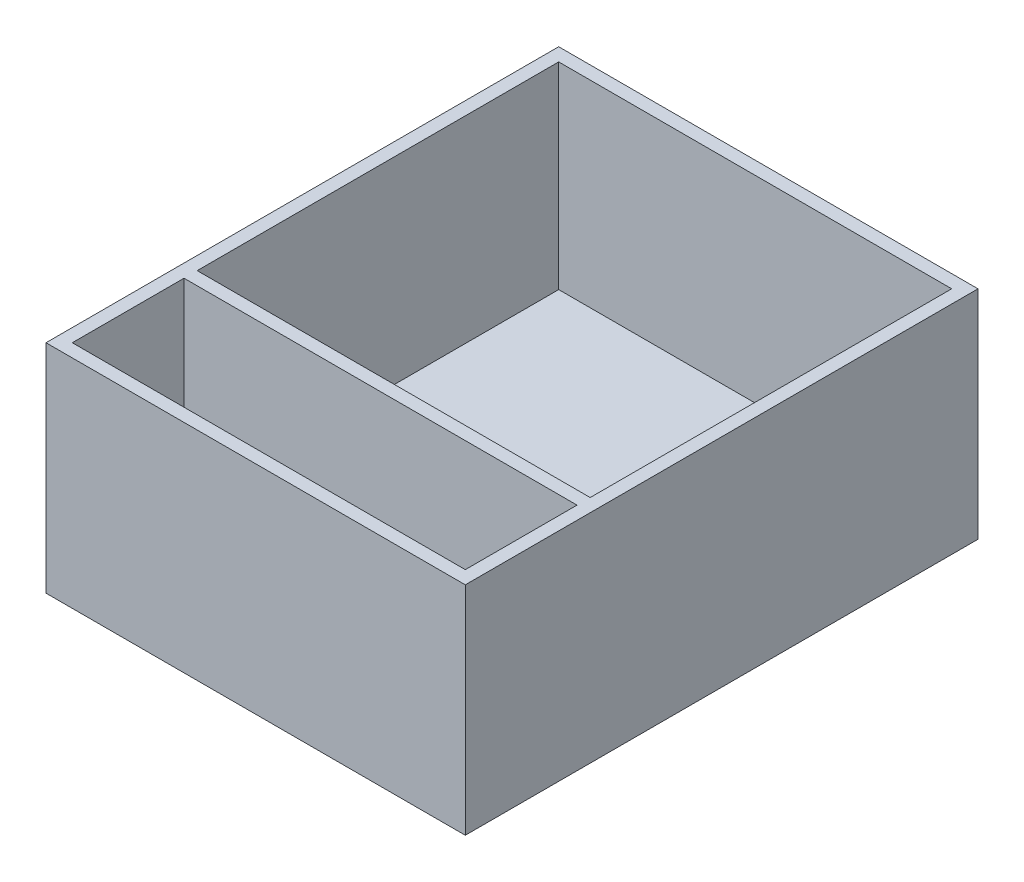
SolidWorks part; units mm, degrees
ref_plane "Front Plane" through (0, 0, 0) normal (0, 0, 1) x (1, 0, 0)
ref_plane "Top Plane" through (0, 0, 0) normal (0, 1, 0) x (1, 0, 0)
ref_plane "Right Plane" through (0, 0, 0) normal (1, 0, 0) x (0, 0, -1)
sketch "Sketch1" plane through (0, 0, 0) normal (0, 1, 0) x (1, 0, 0)
  line L0 (2.6203, -51.9542) -> (2.6263, -51.9542)
  line L1 (2.6263, -51.9542) -> (2.6323, -51.9562)
  line L2 (2.6323, -51.9562) -> (2.6393, -51.9572)
  line L3 (2.6393, -51.9572) -> (2.6443, -51.9602)
  line L4 (2.6443, -51.9602) -> (2.6513, -51.9622)
  line L5 (2.6513, -51.9622) -> (2.6563, -51.9672)
  line L6 (2.6563, -51.9672) -> (2.6613, -51.9702)
  line L7 (2.6613, -51.9702) -> (2.6653, -51.9752)
  line L8 (2.6653, -51.9752) -> (2.6703, -51.9792)
  line L9 (2.6703, -51.9792) -> (2.6743, -51.9852)
  line L10 (2.6743, -51.9852) -> (2.6783, -51.9902)
  line L11 (2.6783, -51.9902) -> (2.6803, -51.9962)
  line L12 (2.6803, -51.9962) -> (2.6843, -52.0022)
  line L13 (2.6843, -52.0022) -> (2.6853, -52.0082)
  line L14 (2.6853, -52.0082) -> (2.6873, -52.0142)
  line L15 (2.6873, -52.0142) -> (2.6873, -52.0212)
  line L16 (2.6873, -52.0212) -> (2.6883, -52.0272)
  line L17 (2.6883, -52.0272) -> (2.6883, -53.0272)
  line L18 (2.6883, -53.0272) -> (2.6873, -53.0342)
  line L19 (2.6873, -53.0342) -> (2.6873, -53.0402)
  line L20 (2.6873, -53.0402) -> (2.6853, -53.0472)
  line L21 (2.6853, -53.0472) -> (2.6843, -53.0532)
  line L22 (2.6843, -53.0532) -> (2.6803, -53.0592)
  line L23 (2.6803, -53.0592) -> (2.6783, -53.0652)
  line L24 (2.6783, -53.0652) -> (2.6743, -53.0702)
  line L25 (2.6743, -53.0702) -> (2.6703, -53.0762)
  line L26 (2.6703, -53.0762) -> (2.6653, -53.0802)
  line L27 (2.6653, -53.0802) -> (2.6613, -53.0852)
  line L28 (2.6613, -53.0852) -> (2.6563, -53.0882)
  line L29 (2.6563, -53.0882) -> (2.6513, -53.0922)
  line L30 (2.6513, -53.0922) -> (2.6443, -53.0952)
  line L31 (2.6443, -53.0952) -> (2.6393, -53.0982)
  line L32 (2.6393, -53.0982) -> (2.6323, -53.0992)
  line L33 (2.6323, -53.0992) -> (2.6263, -53.1012)
  line L34 (2.6263, -53.1012) -> (2.6203, -53.1012)
  line L35 (2.6203, -53.1012) -> (2.6133, -53.1022)
  line L36 (2.6133, -53.1022) -> (2.2323, -53.1022)
  line L37 (2.2323, -53.1022) -> (2.2283, -53.1022)
  line L38 (2.2283, -53.1022) -> (2.2243, -53.1022)
  line L39 (2.2243, -53.1022) -> (2.2153, -53.0992)
  line L40 (2.2153, -53.0992) -> (2.2063, -53.0982)
  line L41 (2.2063, -53.0982) -> (2.2033, -53.0962)
  line L42 (2.2033, -53.0962) -> (2.1993, -53.0942)
  line L43 (2.1993, -53.0942) -> (2.1033, -53.0472)
  line L44 (2.1033, -53.0472) -> (2.0943, -53.0402)
  line L45 (2.0943, -53.0402) -> (2.0843, -53.0332)
  line L46 (2.0843, -53.0332) -> (2.0363, -52.9852)
  line L47 (2.0363, -52.9852) -> (2.0293, -52.9752)
  line L48 (2.0293, -52.9752) -> (2.0223, -52.9662)
  line L49 (2.0223, -52.9662) -> (1.9753, -52.8702)
  line L50 (1.9753, -52.8702) -> (1.9733, -52.8662)
  line L51 (1.9733, -52.8662) -> (1.9713, -52.8632)
  line L52 (1.9713, -52.8632) -> (1.9703, -52.8542)
  line L53 (1.9703, -52.8542) -> (1.9673, -52.8452)
  line L54 (1.9673, -52.8452) -> (1.9673, -52.8412)
  line L55 (1.9673, -52.8412) -> (1.9673, -52.8372)
  line L56 (1.9673, -52.8372) -> (1.9673, -52.6942)
  line L57 (1.9673, -52.6942) -> (1.9673, -52.6902)
  line L58 (1.9673, -52.6902) -> (1.9673, -52.6852)
  line L59 (1.9673, -52.6852) -> (1.9703, -52.6772)
  line L60 (1.9703, -52.6772) -> (1.9713, -52.6682)
  line L61 (1.9713, -52.6682) -> (1.9733, -52.6652)
  line L62 (1.9733, -52.6652) -> (1.9753, -52.6612)
  line L63 (1.9753, -52.6612) -> (2.0223, -52.5652)
  line L64 (2.0223, -52.5652) -> (2.0293, -52.5562)
  line L65 (2.0293, -52.5562) -> (2.0363, -52.5462)
  line L66 (2.0363, -52.5462) -> (2.0843, -52.4982)
  line L67 (2.0843, -52.4982) -> (2.0873, -52.4962)
  line L68 (2.0873, -52.4962) -> (2.0903, -52.4922)
  line L69 (2.0903, -52.4922) -> (2.0983, -52.4882)
  line L70 (2.0983, -52.4882) -> (2.1053, -52.4832)
  line L71 (2.1053, -52.4832) -> (2.1063, -52.4832)
  line L72 (2.1063, -52.4832) -> (2.0843, -52.4612)
  line L73 (2.0843, -52.4612) -> (2.0773, -52.4522)
  line L74 (2.0773, -52.4522) -> (2.0703, -52.4422)
  line L75 (2.0703, -52.4422) -> (2.0223, -52.3472)
  line L76 (2.0223, -52.3472) -> (2.0213, -52.3422)
  line L77 (2.0213, -52.3422) -> (2.0193, -52.3392)
  line L78 (2.0193, -52.3392) -> (2.0173, -52.3302)
  line L79 (2.0173, -52.3302) -> (2.0153, -52.3222)
  line L80 (2.0153, -52.3222) -> (2.0153, -52.3172)
  line L81 (2.0153, -52.3172) -> (2.0143, -52.3132)
  line L82 (2.0143, -52.3132) -> (2.0143, -52.2182)
  line L83 (2.0143, -52.2182) -> (2.0153, -52.2142)
  line L84 (2.0153, -52.2142) -> (2.0153, -52.2092)
  line L85 (2.0153, -52.2092) -> (2.0173, -52.2012)
  line L86 (2.0173, -52.2012) -> (2.0193, -52.1922)
  line L87 (2.0193, -52.1922) -> (2.0213, -52.1882)
  line L88 (2.0213, -52.1882) -> (2.0223, -52.1842)
  line L89 (2.0223, -52.1842) -> (2.0703, -52.0892)
  line L90 (2.0703, -52.0892) -> (2.0773, -52.0792)
  line L91 (2.0773, -52.0792) -> (2.0843, -52.0702)
  line L92 (2.0843, -52.0702) -> (2.1313, -52.0222)
  line L93 (2.1313, -52.0222) -> (2.1413, -52.0152)
  line L94 (2.1413, -52.0152) -> (2.1513, -52.0082)
  line L95 (2.1513, -52.0082) -> (2.2463, -51.9602)
  line L96 (2.2463, -51.9602) -> (2.2503, -51.9592)
  line L97 (2.2503, -51.9592) -> (2.2543, -51.9572)
  line L98 (2.2543, -51.9572) -> (2.2633, -51.9552)
  line L99 (2.2633, -51.9552) -> (2.2713, -51.9532)
  line L100 (2.2713, -51.9532) -> (2.2753, -51.9532)
  line L101 (2.2753, -51.9532) -> (2.2803, -51.9522)
  line L102 (2.2803, -51.9522) -> (2.6133, -51.9522)
  line L103 (2.6133, -51.9522) -> (2.6203, -51.9542)
  line L104 (2.2923, -52.5792) -> (2.1773, -52.6172)
  line L105 (2.1773, -52.6172) -> (2.1513, -52.6432)
  line L106 (2.1513, -52.6432) -> (2.1173, -52.7122)
  line L107 (2.1173, -52.7122) -> (2.1173, -52.8192)
  line L108 (2.1173, -52.8192) -> (2.1513, -52.8882)
  line L109 (2.1513, -52.8882) -> (2.1813, -52.9182)
  line L110 (2.1813, -52.9182) -> (2.2503, -52.9522)
  line L111 (2.2503, -52.9522) -> (2.5383, -52.9522)
  line L112 (2.5383, -52.9522) -> (2.5383, -52.5792)
  line L113 (2.5383, -52.5792) -> (2.2923, -52.5792)
  line L114 (2.2973, -52.1022) -> (2.2293, -52.1372)
  line L115 (2.2293, -52.1372) -> (2.1983, -52.1672)
  line L116 (2.1983, -52.1672) -> (2.1643, -52.2362)
  line L117 (2.1643, -52.2362) -> (2.1643, -52.2952)
  line L118 (2.1643, -52.2952) -> (2.1983, -52.3642)
  line L119 (2.1983, -52.3642) -> (2.2293, -52.3942)
  line L120 (2.2293, -52.3942) -> (2.2973, -52.4292)
  line L121 (2.2973, -52.4292) -> (2.5383, -52.4292)
  line L122 (2.5383, -52.4292) -> (2.5383, -52.1022)
  line L123 (2.5383, -52.1022) -> (2.2973, -52.1022)
  line L124 (0.6173, -51.9542) -> (0.6263, -51.9542)
  line L125 (0.6263, -51.9542) -> (0.6303, -51.9552)
  line L126 (0.6303, -51.9552) -> (0.6343, -51.9552)
  line L127 (0.6343, -51.9552) -> (0.6423, -51.9592)
  line L128 (0.6423, -51.9592) -> (0.6513, -51.9622)
  line L129 (0.6513, -51.9622) -> (0.6543, -51.9652)
  line L130 (0.6543, -51.9652) -> (0.6573, -51.9672)
  line L131 (0.6573, -51.9672) -> (0.6643, -51.9732)
  line L132 (0.6643, -51.9732) -> (0.6703, -51.9792)
  line L133 (0.6703, -51.9792) -> (0.6733, -51.9832)
  line L134 (0.6733, -51.9832) -> (0.6753, -51.9862)
  line L135 (0.6753, -51.9862) -> (0.7673, -52.1222)
  line L136 (0.7673, -52.1222) -> (0.8483, -52.2042)
  line L137 (0.8483, -52.2042) -> (0.9323, -52.2462)
  line L138 (0.9323, -52.2462) -> (0.9533, -52.2622)
  line L139 (0.9533, -52.2622) -> (0.9683, -52.2832)
  line L140 (0.9683, -52.2832) -> (0.9743, -52.3092)
  line L141 (0.9743, -52.3092) -> (0.9713, -52.3342)
  line L142 (0.9713, -52.3342) -> (0.9593, -52.3582)
  line L143 (0.9593, -52.3582) -> (0.9403, -52.3762)
  line L144 (0.9403, -52.3762) -> (0.9163, -52.3862)
  line L145 (0.9163, -52.3862) -> (0.8903, -52.3882)
  line L146 (0.8903, -52.3882) -> (0.8653, -52.3802)
  line L147 (0.8653, -52.3802) -> (0.7703, -52.3332)
  line L148 (0.7703, -52.3332) -> (0.7603, -52.3252)
  line L149 (0.7603, -52.3252) -> (0.7503, -52.3192)
  line L150 (0.7503, -52.3192) -> (0.6883, -52.2562)
  line L151 (0.6883, -52.2562) -> (0.6883, -52.9522)
  line L152 (0.6883, -52.9522) -> (0.8993, -52.9522)
  line L153 (0.8993, -52.9522) -> (0.9243, -52.9572)
  line L154 (0.9243, -52.9572) -> (0.9473, -52.9702)
  line L155 (0.9473, -52.9702) -> (0.9643, -52.9902)
  line L156 (0.9643, -52.9902) -> (0.9733, -53.0142)
  line L157 (0.9733, -53.0142) -> (0.9733, -53.0402)
  line L158 (0.9733, -53.0402) -> (0.9643, -53.0652)
  line L159 (0.9643, -53.0652) -> (0.9473, -53.0852)
  line L160 (0.9473, -53.0852) -> (0.9243, -53.0982)
  line L161 (0.9243, -53.0982) -> (0.8993, -53.1022)
  line L162 (0.8993, -53.1022) -> (0.3273, -53.1022)
  line L163 (0.3273, -53.1022) -> (0.3023, -53.0982)
  line L164 (0.3023, -53.0982) -> (0.2793, -53.0852)
  line L165 (0.2793, -53.0852) -> (0.2623, -53.0652)
  line L166 (0.2623, -53.0652) -> (0.2533, -53.0402)
  line L167 (0.2533, -53.0402) -> (0.2533, -53.0142)
  line L168 (0.2533, -53.0142) -> (0.2623, -52.9902)
  line L169 (0.2623, -52.9902) -> (0.2793, -52.9702)
  line L170 (0.2793, -52.9702) -> (0.3023, -52.9572)
  line L171 (0.3023, -52.9572) -> (0.3273, -52.9522)
  line L172 (0.3273, -52.9522) -> (0.5383, -52.9522)
  line L173 (0.5383, -52.9522) -> (0.5383, -52.0272)
  line L174 (0.5383, -52.0272) -> (0.5393, -52.0232)
  line L175 (0.5393, -52.0232) -> (0.5393, -52.0192)
  line L176 (0.5393, -52.0192) -> (0.5413, -52.0112)
  line L177 (0.5413, -52.0112) -> (0.5433, -52.0022)
  line L178 (0.5433, -52.0022) -> (0.5453, -51.9982)
  line L179 (0.5453, -51.9982) -> (0.5463, -51.9942)
  line L180 (0.5463, -51.9942) -> (0.5513, -51.9872)
  line L181 (0.5513, -51.9872) -> (0.5563, -51.9792)
  line L182 (0.5563, -51.9792) -> (0.5593, -51.9762)
  line L183 (0.5593, -51.9762) -> (0.5613, -51.9732)
  line L184 (0.5613, -51.9732) -> (0.5693, -51.9682)
  line L185 (0.5693, -51.9682) -> (0.5763, -51.9622)
  line L186 (0.5763, -51.9622) -> (0.5793, -51.9612)
  line L187 (0.5793, -51.9612) -> (0.5833, -51.9592)
  line L188 (0.5833, -51.9592) -> (0.5923, -51.9572)
  line L189 (0.5923, -51.9572) -> (0.6003, -51.9542)
  line L190 (0.6003, -51.9542) -> (0.6043, -51.9542)
  line L191 (0.6043, -51.9542) -> (0.6083, -51.9532)
  line L192 (0.6083, -51.9532) -> (0.6173, -51.9542)
  line L193 (1.7823, -51.9572) -> (1.8043, -51.9702)
  line L194 (1.8043, -51.9702) -> (1.8213, -51.9902)
  line L195 (1.8213, -51.9902) -> (1.8303, -52.0142)
  line L196 (1.8303, -52.0142) -> (1.8303, -52.0402)
  line L197 (1.8303, -52.0402) -> (1.8213, -52.0652)
  line L198 (1.8213, -52.0652) -> (1.8043, -52.0852)
  line L199 (1.8043, -52.0852) -> (1.7823, -52.0982)
  line L200 (1.7823, -52.0982) -> (1.7563, -52.1022)
  line L201 (1.7563, -52.1022) -> (1.5453, -52.1022)
  line L202 (1.5453, -52.1022) -> (1.5453, -53.0272)
  line L203 (1.5453, -53.0272) -> (1.5413, -53.0532)
  line L204 (1.5413, -53.0532) -> (1.5283, -53.0762)
  line L205 (1.5283, -53.0762) -> (1.5083, -53.0922)
  line L206 (1.5083, -53.0922) -> (1.4833, -53.1012)
  line L207 (1.4833, -53.1012) -> (1.4573, -53.1012)
  line L208 (1.4573, -53.1012) -> (1.4333, -53.0922)
  line L209 (1.4333, -53.0922) -> (1.4133, -53.0762)
  line L210 (1.4133, -53.0762) -> (1.4003, -53.0532)
  line L211 (1.4003, -53.0532) -> (1.3953, -53.0272)
  line L212 (1.3953, -53.0272) -> (1.3953, -52.1022)
  line L213 (1.3953, -52.1022) -> (1.1843, -52.1022)
  line L214 (1.1843, -52.1022) -> (1.1593, -52.0982)
  line L215 (1.1593, -52.0982) -> (1.1363, -52.0852)
  line L216 (1.1363, -52.0852) -> (1.1203, -52.0652)
  line L217 (1.1203, -52.0652) -> (1.1113, -52.0402)
  line L218 (1.1113, -52.0402) -> (1.1113, -52.0142)
  line L219 (1.1113, -52.0142) -> (1.1203, -51.9902)
  line L220 (1.1203, -51.9902) -> (1.1363, -51.9702)
  line L221 (1.1363, -51.9702) -> (1.1593, -51.9572)
  line L222 (1.1593, -51.9572) -> (1.1843, -51.9522)
  line L223 (1.1843, -51.9522) -> (1.7563, -51.9522)
  line L224 (1.7563, -51.9522) -> (1.7823, -51.9572)
  line L225 (28.7293, -19.6352) -> (28.7353, -19.6352)
  line L226 (28.7353, -19.6352) -> (28.7403, -19.637)
  line L227 (28.7403, -19.637) -> (28.7453, -19.6379)
  line L228 (28.7453, -19.6379) -> (28.7493, -19.6406)
  line L229 (28.7493, -19.6406) -> (28.7543, -19.6424)
  line L230 (28.7543, -19.6424) -> (28.7593, -19.6459)
  line L231 (28.7593, -19.6459) -> (28.7633, -19.6485)
  line L232 (28.7633, -19.6485) -> (28.7673, -19.6526)
  line L233 (28.7673, -19.6526) -> (28.7713, -19.656)
  line L234 (28.7713, -19.656) -> (28.7733, -19.6607)
  line L235 (28.7733, -19.6607) -> (28.7773, -19.6647)
  line L236 (28.7773, -19.6647) -> (28.7793, -19.6697)
  line L237 (28.7793, -19.6697) -> (28.7813, -19.6744)
  line L238 (28.7813, -19.6744) -> (28.7823, -19.6796)
  line L239 (28.7823, -19.6796) -> (28.7843, -19.6846)
  line L240 (28.7843, -19.6846) -> (28.7843, -19.6899)
  line L241 (28.7843, -19.69) -> (28.7843, -49.9002)
  line L242 (28.7843, -49.9002) -> (28.7843, -49.9062)
  line L243 (28.7843, -49.9062) -> (28.7823, -49.9112)
  line L244 (28.7823, -49.9112) -> (28.7813, -49.9162)
  line L245 (28.7813, -49.9162) -> (28.7793, -49.9202)
  line L246 (28.7793, -49.9202) -> (28.7773, -49.9252)
  line L247 (28.7773, -49.9252) -> (28.7733, -49.9302)
  line L248 (28.7733, -49.9302) -> (28.7713, -49.9342)
  line L249 (28.7713, -49.9342) -> (28.7673, -49.9382)
  line L250 (28.7673, -49.9382) -> (28.7633, -49.9422)
  line L251 (28.7633, -49.9422) -> (28.7593, -49.9442)
  line L252 (28.7593, -49.9442) -> (28.7543, -49.9482)
  line L253 (28.7543, -49.9482) -> (28.7493, -49.9502)
  line L254 (28.7493, -49.9502) -> (28.7453, -49.9522)
  line L255 (28.7453, -49.9522) -> (28.7403, -49.9532)
  line L256 (28.7403, -49.9532) -> (28.7353, -49.9552)
  line L257 (28.7353, -49.9552) -> (28.7293, -49.9552)
  line L258 (28.7293, -49.9552) -> (-25.7807, -49.9552)
  line L259 (-25.7807, -49.9552) -> (-25.7867, -49.9552)
  line L260 (-25.7867, -49.9552) -> (-25.7917, -49.9532)
  line L261 (-25.7917, -49.9532) -> (-25.7967, -49.9522)
  line L262 (-25.7967, -49.9522) -> (-25.8007, -49.9502)
  line L263 (-25.8007, -49.9502) -> (-25.8057, -49.9482)
  line L264 (-25.8057, -49.9482) -> (-25.8107, -49.9442)
  line L265 (-25.8107, -49.9442) -> (-25.8147, -49.9422)
  line L266 (-25.8147, -49.9422) -> (-25.8187, -49.9382)
  line L267 (-25.8187, -49.9382) -> (-25.8227, -49.9342)
  line L268 (-25.8227, -49.9342) -> (-25.8247, -49.9302)
  line L269 (-25.8247, -49.9302) -> (-25.8287, -49.9252)
  line L270 (-25.8287, -49.9252) -> (-25.8307, -49.9202)
  line L271 (-25.8307, -49.9202) -> (-25.8327, -49.9162)
  line L272 (-25.8327, -49.9162) -> (-25.8337, -49.9112)
  line L273 (-25.8337, -49.9112) -> (-25.8357, -49.9062)
  line L274 (-25.8357, -49.9062) -> (-25.8357, -49.8842)
  line L275 (-25.8357, -49.8842) -> (-25.8357, -19.69)
  line L276 (-25.8357, -19.6899) -> (-25.8357, -19.6846)
  line L277 (-25.8357, -19.6846) -> (-25.8337, -19.6796)
  line L278 (-25.8337, -19.6796) -> (-25.8327, -19.6744)
  line L279 (-25.8327, -19.6744) -> (-25.8307, -19.6697)
  line L280 (-25.8307, -19.6697) -> (-25.8287, -19.6647)
  line L281 (-25.8287, -19.6647) -> (-25.8247, -19.6607)
  line L282 (-25.8247, -19.6607) -> (-25.8227, -19.656)
  line L283 (-25.8227, -19.656) -> (-25.8187, -19.6526)
  line L284 (-25.8187, -19.6526) -> (-25.8147, -19.6485)
  line L285 (-25.8147, -19.6485) -> (-25.8107, -19.6459)
  line L286 (-25.8107, -19.6459) -> (-25.8057, -19.6424)
  line L287 (-25.8057, -19.6424) -> (-25.8007, -19.6406)
  line L288 (-25.8007, -19.6406) -> (-25.7967, -19.6379)
  line L289 (-25.7967, -19.6379) -> (-25.7917, -19.637)
  line L290 (-25.7917, -19.637) -> (-25.7867, -19.6352)
  line L291 (-25.7867, -19.6352) -> (-25.7807, -19.6352)
  line L292 (-25.7807, -19.6352) -> (28.7293, -19.6352)
  line L293 (-25.7157, -19.7552) -> (-25.7157, -49.8352)
  line L294 (-25.7157, -49.8352) -> (28.6643, -49.8352)
  line L295 (28.6643, -49.8352) -> (28.6643, -19.7552)
  line L296 (28.6643, -19.7552) -> (-25.7157, -19.7552)
  line L297 (21.6883, -15.0497) -> (21.7003, -15.0514)
  line L298 (21.7003, -15.0514) -> (21.8433, -15.099)
  line L299 (21.8433, -15.099) -> (21.8473, -15.1011)
  line L300 (21.8473, -15.1011) -> (21.8513, -15.1022)
  line L301 (21.8513, -15.1022) -> (21.8583, -15.1073)
  line L302 (21.8583, -15.1073) -> (21.8663, -15.1115)
  line L303 (21.8663, -15.1115) -> (21.8693, -15.1147)
  line L304 (21.8693, -15.1147) -> (21.8723, -15.1172)
  line L305 (21.8723, -15.1172) -> (21.9683, -15.2124)
  line L306 (21.9683, -15.2124) -> (21.9743, -15.2222)
  line L307 (21.9743, -15.2222) -> (21.9823, -15.2319)
  line L308 (21.9823, -15.2319) -> (22.0293, -15.3271)
  line L309 (22.0293, -15.3271) -> (22.0323, -15.335)
  line L310 (22.0323, -15.335) -> (22.0353, -15.3425)
  line L311 (22.0353, -15.3425) -> (22.0823, -15.533)
  line L312 (22.0823, -15.533) -> (22.0833, -15.5421)
  line L313 (22.0833, -15.5421) -> (22.0853, -15.5512)
  line L314 (22.0853, -15.5512) -> (22.0853, -15.694)
  line L315 (22.0853, -15.694) -> (22.0833, -15.703)
  line L316 (22.0833, -15.703) -> (22.0823, -15.7122)
  line L317 (22.0823, -15.7122) -> (22.0353, -15.9027)
  line L318 (22.0353, -15.9027) -> (22.0323, -15.9102)
  line L319 (22.0323, -15.9102) -> (22.0293, -15.918)
  line L320 (22.0293, -15.918) -> (21.9823, -16.0133)
  line L321 (21.9823, -16.0133) -> (21.9743, -16.0229)
  line L322 (21.9743, -16.0229) -> (21.9683, -16.0328)
  line L323 (21.9683, -16.0328) -> (21.8723, -16.128)
  line L324 (21.8723, -16.128) -> (21.8693, -16.1305)
  line L325 (21.8693, -16.1305) -> (21.8663, -16.1337)
  line L326 (21.8663, -16.1337) -> (21.8583, -16.1379)
  line L327 (21.8583, -16.1379) -> (21.8513, -16.1429)
  line L328 (21.8513, -16.1429) -> (21.8473, -16.1441)
  line L329 (21.8473, -16.1441) -> (21.8433, -16.1461)
  line L330 (21.8433, -16.1461) -> (21.7003, -16.1937)
  line L331 (21.7003, -16.1937) -> (21.6883, -16.1955)
  line L332 (21.6883, -16.1955) -> (21.6763, -16.1976)
  line L333 (21.6763, -16.1976) -> (21.5813, -16.1976)
  line L334 (21.5813, -16.1976) -> (21.5693, -16.1955)
  line L335 (21.5693, -16.1955) -> (21.5573, -16.1937)
  line L336 (21.5573, -16.1937) -> (21.4153, -16.1461)
  line L337 (21.4153, -16.1461) -> (21.4113, -16.1441)
  line L338 (21.4113, -16.1441) -> (21.4073, -16.1429)
  line L339 (21.4073, -16.1429) -> (21.3993, -16.1379)
  line L340 (21.3993, -16.1379) -> (21.3923, -16.1337)
  line L341 (21.3923, -16.1337) -> (21.3893, -16.1305)
  line L342 (21.3893, -16.1305) -> (21.3853, -16.128)
  line L343 (21.3853, -16.128) -> (21.3383, -16.0804)
  line L344 (21.3383, -16.0804) -> (21.3233, -16.059)
  line L345 (21.3233, -16.059) -> (21.3163, -16.0339)
  line L346 (21.3163, -16.0339) -> (21.3183, -16.0079)
  line L347 (21.3183, -16.0079) -> (21.3293, -15.9843)
  line L348 (21.3293, -15.9843) -> (21.3483, -15.9659)
  line L349 (21.3483, -15.9659) -> (21.3713, -15.9549)
  line L350 (21.3713, -15.9549) -> (21.3973, -15.9526)
  line L351 (21.3973, -15.9526) -> (21.4223, -15.9594)
  line L352 (21.4223, -15.9594) -> (21.4443, -15.9743)
  line L353 (21.4443, -15.9743) -> (21.4793, -16.0094)
  line L354 (21.4793, -16.0094) -> (21.5933, -16.0476)
  line L355 (21.5933, -16.0476) -> (21.6643, -16.0476)
  line L356 (21.6643, -16.0476) -> (21.7793, -16.0094)
  line L357 (21.7793, -16.0094) -> (21.8533, -15.9353)
  line L358 (21.8533, -15.9353) -> (21.8913, -15.8583)
  line L359 (21.8913, -15.8583) -> (21.9353, -15.6848)
  line L360 (21.9353, -15.6848) -> (21.9353, -15.5604)
  line L361 (21.9353, -15.5604) -> (21.8913, -15.3869)
  line L362 (21.8913, -15.3869) -> (21.8533, -15.3099)
  line L363 (21.8533, -15.3099) -> (21.7793, -15.2358)
  line L364 (21.7793, -15.2358) -> (21.6643, -15.1976)
  line L365 (21.6643, -15.1976) -> (21.5933, -15.1976)
  line L366 (21.5933, -15.1976) -> (21.4793, -15.2358)
  line L367 (21.4793, -15.2358) -> (21.4443, -15.2709)
  line L368 (21.4443, -15.2709) -> (21.4223, -15.2858)
  line L369 (21.4223, -15.2858) -> (21.3973, -15.2925)
  line L370 (21.3973, -15.2925) -> (21.3713, -15.2903)
  line L371 (21.3713, -15.2903) -> (21.3483, -15.2793)
  line L372 (21.3483, -15.2793) -> (21.3293, -15.2608)
  line L373 (21.3293, -15.2608) -> (21.3183, -15.2372)
  line L374 (21.3183, -15.2372) -> (21.3163, -15.2113)
  line L375 (21.3163, -15.2113) -> (21.3233, -15.1861)
  line L376 (21.3233, -15.1861) -> (21.3383, -15.1648)
  line L377 (21.3383, -15.1648) -> (21.3853, -15.1172)
  line L378 (21.3853, -15.1172) -> (21.3893, -15.1147)
  line L379 (21.3893, -15.1147) -> (21.3923, -15.1115)
  line L380 (21.3923, -15.1115) -> (21.3993, -15.1073)
  line L381 (21.3993, -15.1073) -> (21.4073, -15.1022)
  line L382 (21.4073, -15.1022) -> (21.4113, -15.1011)
  line L383 (21.4113, -15.1011) -> (21.4153, -15.099)
  line L384 (21.4153, -15.099) -> (21.5573, -15.0514)
  line L385 (21.5573, -15.0514) -> (21.5693, -15.0497)
  line L386 (21.5693, -15.0497) -> (21.5813, -15.0476)
  line L387 (21.5813, -15.0476) -> (21.6763, -15.0476)
  line L388 (21.6763, -15.0476) -> (21.6883, -15.0497)
  line L389 (20.8233, -15.0483) -> (20.8283, -15.0481)
  line L390 (20.8283, -15.0481) -> (20.8363, -15.0506)
  line L391 (20.8363, -15.0506) -> (20.8453, -15.0521)
  line L392 (20.8453, -15.0521) -> (20.8493, -15.0543)
  line L393 (20.8493, -15.0543) -> (20.8533, -15.0555)
  line L394 (20.8533, -15.0555) -> (20.9483, -15.1031)
  line L395 (20.9483, -15.1031) -> (20.9583, -15.1103)
  line L396 (20.9583, -15.1103) -> (20.9683, -15.1172)
  line L397 (20.9683, -15.1172) -> (21.0153, -15.1648)
  line L398 (21.0153, -15.1648) -> (21.0223, -15.1746)
  line L399 (21.0223, -15.1746) -> (21.0293, -15.1843)
  line L400 (21.0293, -15.1843) -> (21.0773, -15.2795)
  line L401 (21.0773, -15.2795) -> (21.0783, -15.2837)
  line L402 (21.0783, -15.2837) -> (21.0803, -15.2874)
  line L403 (21.0803, -15.2874) -> (21.0823, -15.2961)
  line L404 (21.0823, -15.2961) -> (21.0843, -15.3045)
  line L405 (21.0843, -15.3045) -> (21.0843, -15.3088)
  line L406 (21.0843, -15.3088) -> (21.0853, -15.3131)
  line L407 (21.0853, -15.3131) -> (21.0853, -15.3607)
  line L408 (21.0853, -15.3607) -> (21.0843, -15.3649)
  line L409 (21.0843, -15.3649) -> (21.0843, -15.3693)
  line L410 (21.0843, -15.3693) -> (21.0823, -15.3777)
  line L411 (21.0823, -15.3777) -> (21.0803, -15.3863)
  line L412 (21.0803, -15.3863) -> (21.0783, -15.3901)
  line L413 (21.0783, -15.3901) -> (21.0773, -15.3942)
  line L414 (21.0773, -15.3942) -> (21.0293, -15.4895)
  line L415 (21.0293, -15.4895) -> (21.0223, -15.4991)
  line L416 (21.0223, -15.4991) -> (21.0153, -15.5089)
  line L417 (21.0153, -15.5089) -> (20.9733, -15.5512)
  line L418 (20.9733, -15.5512) -> (21.0153, -15.5934)
  line L419 (21.0153, -15.5934) -> (21.0223, -15.6032)
  line L420 (21.0223, -15.6032) -> (21.0293, -15.6128)
  line L421 (21.0293, -15.6128) -> (21.0773, -15.7081)
  line L422 (21.0773, -15.7081) -> (21.0783, -15.7122)
  line L423 (21.0783, -15.7122) -> (21.0803, -15.716)
  line L424 (21.0803, -15.716) -> (21.0823, -15.7246)
  line L425 (21.0823, -15.7246) -> (21.0843, -15.7331)
  line L426 (21.0843, -15.7331) -> (21.0843, -15.7374)
  line L427 (21.0843, -15.7374) -> (21.0853, -15.7416)
  line L428 (21.0853, -15.7416) -> (21.0853, -15.9321)
  line L429 (21.0853, -15.9321) -> (21.0843, -15.9364)
  line L430 (21.0843, -15.9364) -> (21.0843, -15.9407)
  line L431 (21.0843, -15.9407) -> (21.0823, -15.9491)
  line L432 (21.0823, -15.9491) -> (21.0803, -15.9578)
  line L433 (21.0803, -15.9578) -> (21.0783, -15.9615)
  line L434 (21.0783, -15.9615) -> (21.0773, -15.9656)
  line L435 (21.0773, -15.9656) -> (21.0293, -16.0609)
  line L436 (21.0293, -16.0609) -> (21.0223, -16.0705)
  line L437 (21.0223, -16.0705) -> (21.0153, -16.0804)
  line L438 (21.0153, -16.0804) -> (20.9683, -16.128)
  line L439 (20.9683, -16.128) -> (20.9583, -16.1349)
  line L440 (20.9583, -16.1349) -> (20.9483, -16.142)
  line L441 (20.9483, -16.142) -> (20.8533, -16.1897)
  line L442 (20.8533, -16.1897) -> (20.8493, -16.1909)
  line L443 (20.8493, -16.1909) -> (20.8453, -16.1931)
  line L444 (20.8453, -16.1931) -> (20.8363, -16.1946)
  line L445 (20.8363, -16.1946) -> (20.8283, -16.1971)
  line L446 (20.8283, -16.1971) -> (20.8233, -16.1968)
  line L447 (20.8233, -16.1968) -> (20.8193, -16.1976)
  line L448 (20.8193, -16.1976) -> (20.6293, -16.1976)
  line L449 (20.6293, -16.1976) -> (20.6253, -16.1968)
  line L450 (20.6253, -16.1968) -> (20.6203, -16.1971)
  line L451 (20.6203, -16.1971) -> (20.6123, -16.1946)
  line L452 (20.6123, -16.1946) -> (20.6033, -16.1931)
  line L453 (20.6033, -16.1931) -> (20.5993, -16.1909)
  line L454 (20.5993, -16.1909) -> (20.5953, -16.1897)
  line L455 (20.5953, -16.1897) -> (20.5003, -16.142)
  line L456 (20.5003, -16.142) -> (20.4903, -16.1349)
  line L457 (20.4903, -16.1349) -> (20.4803, -16.128)
  line L458 (20.4803, -16.128) -> (20.4333, -16.0804)
  line L459 (20.4333, -16.0804) -> (20.4263, -16.0705)
  line L460 (20.4263, -16.0705) -> (20.4193, -16.0609)
  line L461 (20.4193, -16.0609) -> (20.3713, -15.9656)
  line L462 (20.3713, -15.9656) -> (20.3703, -15.9615)
  line L463 (20.3703, -15.9615) -> (20.3683, -15.9578)
  line L464 (20.3683, -15.9578) -> (20.3663, -15.9491)
  line L465 (20.3663, -15.9491) -> (20.3643, -15.9407)
  line L466 (20.3643, -15.9407) -> (20.3643, -15.9364)
  line L467 (20.3643, -15.9364) -> (20.3633, -15.9321)
  line L468 (20.3633, -15.9321) -> (20.3633, -15.7416)
  line L469 (20.3633, -15.7416) -> (20.3643, -15.7374)
  line L470 (20.3643, -15.7374) -> (20.3643, -15.7331)
  line L471 (20.3643, -15.7331) -> (20.3663, -15.7246)
  line L472 (20.3663, -15.7246) -> (20.3683, -15.716)
  line L473 (20.3683, -15.716) -> (20.3703, -15.7122)
  line L474 (20.3703, -15.7122) -> (20.3713, -15.7081)
  line L475 (20.3713, -15.7081) -> (20.4193, -15.6128)
  line L476 (20.4193, -15.6128) -> (20.4263, -15.6032)
  line L477 (20.4263, -15.6032) -> (20.4333, -15.5934)
  line L478 (20.4333, -15.5934) -> (20.4753, -15.5512)
  line L479 (20.4753, -15.5512) -> (20.4333, -15.5089)
  line L480 (20.4333, -15.5089) -> (20.4263, -15.4991)
  line L481 (20.4263, -15.4991) -> (20.4193, -15.4895)
  line L482 (20.4193, -15.4895) -> (20.3713, -15.3942)
  line L483 (20.3713, -15.3942) -> (20.3703, -15.3901)
  line L484 (20.3703, -15.3901) -> (20.3683, -15.3863)
  line L485 (20.3683, -15.3863) -> (20.3663, -15.3777)
  line L486 (20.3663, -15.3777) -> (20.3643, -15.3692)
  line L487 (20.3643, -15.3692) -> (20.3643, -15.3649)
  line L488 (20.3643, -15.3649) -> (20.3633, -15.3607)
  line L489 (20.3633, -15.3607) -> (20.3633, -15.3131)
  line L490 (20.3633, -15.3131) -> (20.3643, -15.3088)
  line L491 (20.3643, -15.3088) -> (20.3643, -15.3045)
  line L492 (20.3643, -15.3045) -> (20.3663, -15.2961)
  line L493 (20.3663, -15.2961) -> (20.3683, -15.2874)
  line L494 (20.3683, -15.2874) -> (20.3703, -15.2837)
  line L495 (20.3703, -15.2837) -> (20.3713, -15.2795)
  line L496 (20.3713, -15.2795) -> (20.4193, -15.1843)
  line L497 (20.4193, -15.1843) -> (20.4263, -15.1746)
  line L498 (20.4263, -15.1746) -> (20.4333, -15.1648)
  line L499 (20.4333, -15.1648) -> (20.4803, -15.1172)
  line L500 (20.4803, -15.1172) -> (20.4903, -15.1103)
  line L501 (20.4903, -15.1103) -> (20.5003, -15.1031)
  line L502 (20.5003, -15.1031) -> (20.5953, -15.0555)
  line L503 (20.5953, -15.0555) -> (20.5993, -15.0543)
  line L504 (20.5993, -15.0543) -> (20.6033, -15.0521)
  line L505 (20.6033, -15.0521) -> (20.6123, -15.0506)
  line L506 (20.6123, -15.0506) -> (20.6203, -15.0481)
  line L507 (20.6203, -15.0481) -> (20.6253, -15.0483)
  line L508 (20.6253, -15.0483) -> (20.6293, -15.0476)
  line L509 (20.6293, -15.0476) -> (20.8193, -15.0476)
  line L510 (20.8193, -15.0476) -> (20.8233, -15.0483)
  line L511 (20.6463, -15.6262) -> (20.5783, -15.6604)
  line L512 (20.5783, -15.6604) -> (20.5483, -15.6908)
  line L513 (20.5483, -15.6908) -> (20.5133, -15.7593)
  line L514 (20.5133, -15.7593) -> (20.5133, -15.9144)
  line L515 (20.5133, -15.9144) -> (20.5483, -15.9829)
  line L516 (20.5483, -15.9829) -> (20.5783, -16.0133)
  line L517 (20.5783, -16.0133) -> (20.6463, -16.0476)
  line L518 (20.6463, -16.0476) -> (20.8023, -16.0476)
  line L519 (20.8023, -16.0476) -> (20.8703, -16.0133)
  line L520 (20.8703, -16.0133) -> (20.9003, -15.9829)
  line L521 (20.9003, -15.9829) -> (20.9353, -15.9144)
  line L522 (20.9353, -15.9144) -> (20.9353, -15.7593)
  line L523 (20.9353, -15.7593) -> (20.9003, -15.6908)
  line L524 (20.9003, -15.6908) -> (20.8703, -15.6604)
  line L525 (20.8703, -15.6604) -> (20.8023, -15.6262)
  line L526 (20.8023, -15.6262) -> (20.6463, -15.6262)
  line L527 (20.6463, -15.1976) -> (20.5783, -15.2318)
  line L528 (20.5783, -15.2318) -> (20.5483, -15.2622)
  line L529 (20.5483, -15.2622) -> (20.5133, -15.3308)
  line L530 (20.5133, -15.3308) -> (20.5133, -15.343)
  line L531 (20.5133, -15.343) -> (20.5483, -15.4115)
  line L532 (20.5483, -15.4115) -> (20.5783, -15.4419)
  line L533 (20.5783, -15.4419) -> (20.6463, -15.4762)
  line L534 (20.6463, -15.4762) -> (20.8023, -15.4762)
  line L535 (20.8023, -15.4762) -> (20.8703, -15.4419)
  line L536 (20.8703, -15.4419) -> (20.9003, -15.4115)
  line L537 (20.9003, -15.4115) -> (20.9353, -15.343)
  line L538 (20.9353, -15.343) -> (20.9353, -15.3308)
  line L539 (20.9353, -15.3308) -> (20.9003, -15.2622)
  line L540 (20.9003, -15.2622) -> (20.8703, -15.2318)
  line L541 (20.8703, -15.2318) -> (20.8023, -15.1976)
  line L542 (20.8023, -15.1976) -> (20.6463, -15.1976)
  line L543 (21.5033, -14.6729) -> (21.5223, -14.6835)
  line L544 (21.5223, -14.6835) -> (21.5353, -14.6997)
  line L545 (21.5353, -14.6997) -> (21.5433, -14.7196)
  line L546 (21.5433, -14.7196) -> (21.5433, -14.7408)
  line L547 (21.5433, -14.7408) -> (21.5353, -14.7607)
  line L548 (21.5353, -14.7607) -> (21.5223, -14.7769)
  line L549 (21.5223, -14.7769) -> (21.5033, -14.7875)
  line L550 (21.5033, -14.7875) -> (21.4883, -14.7902)
  line L551 (21.4883, -14.7902) -> (20.9603, -14.7902)
  line L552 (20.9603, -14.7902) -> (20.9453, -14.7875)
  line L553 (20.9453, -14.7875) -> (20.9263, -14.7769)
  line L554 (20.9263, -14.7769) -> (20.9133, -14.7607)
  line L555 (20.9133, -14.7607) -> (20.9053, -14.7408)
  line L556 (20.9053, -14.7408) -> (20.9053, -14.7196)
  line L557 (20.9053, -14.7196) -> (20.9133, -14.6997)
  line L558 (20.9133, -14.6997) -> (20.9263, -14.6835)
  line L559 (20.9263, -14.6835) -> (20.9453, -14.6729)
  line L560 (20.9453, -14.6729) -> (20.9603, -14.6702)
  line L561 (20.9603, -14.6702) -> (21.4883, -14.6702)
  line L562 (21.4883, -14.6702) -> (21.5033, -14.6729)
  line L563 (21.5033, -13.2529) -> (21.5223, -13.2635)
  line L564 (21.5223, -13.2635) -> (21.5353, -13.2797)
  line L565 (21.5353, -13.2797) -> (21.5433, -13.2996)
  line L566 (21.5433, -13.2996) -> (21.5433, -13.3208)
  line L567 (21.5433, -13.3208) -> (21.5353, -13.3407)
  line L568 (21.5353, -13.3407) -> (21.5223, -13.3569)
  line L569 (21.5223, -13.3569) -> (21.5033, -13.3675)
  line L570 (21.5033, -13.3675) -> (21.4883, -13.3702)
  line L571 (21.4883, -13.3702) -> (20.9603, -13.3702)
  line L572 (20.9603, -13.3702) -> (20.9453, -13.3675)
  line L573 (20.9453, -13.3675) -> (20.9263, -13.3569)
  line L574 (20.9263, -13.3569) -> (20.9133, -13.3407)
  line L575 (20.9133, -13.3407) -> (20.9053, -13.3208)
  line L576 (20.9053, -13.3208) -> (20.9053, -13.2996)
  line L577 (20.9053, -13.2996) -> (20.9133, -13.2797)
  line L578 (20.9133, -13.2797) -> (20.9263, -13.2635)
  line L579 (20.9263, -13.2635) -> (20.9453, -13.2529)
  line L580 (20.9453, -13.2529) -> (20.9603, -13.2502)
  line L581 (20.9603, -13.2502) -> (21.4883, -13.2502)
  line L582 (21.4883, -13.2502) -> (21.5033, -13.2529)
  line L583 (22.5413, 41.0525) -> (22.5573, 41.0437)
  line L584 (22.5573, 41.0437) -> (22.5683, 41.0302)
  line L585 (22.5683, 41.0302) -> (22.5743, 41.0136)
  line L586 (22.5743, 41.0136) -> (22.5743, 40.996)
  line L587 (22.5743, 40.996) -> (22.5733, 40.9919)
  line L588 (22.5733, 40.9918) -> (22.5743, 40.9859)
  line L589 (22.5743, 40.9859) -> (22.6623, 40.2667)
  line L590 (22.6623, 40.2667) -> (22.9433, 38.9763)
  line L591 (22.9433, 38.9763) -> (23.3773, 37.7297)
  line L592 (23.3773, 37.7297) -> (23.9583, 36.5443)
  line L593 (23.9583, 36.5443) -> (24.6773, 35.4373)
  line L594 (24.6773, 35.4373) -> (25.5243, 34.4247)
  line L595 (25.5243, 34.4247) -> (26.4873, 33.5212)
  line L596 (26.4873, 33.5212) -> (27.5513, 32.7398)
  line L597 (27.5513, 32.7398) -> (28.7013, 32.0919)
  line L598 (28.7013, 32.0919) -> (29.9203, 31.5869)
  line L599 (29.9203, 31.5869) -> (31.1923, 31.2321)
  line L600 (31.1923, 31.2321) -> (32.5003, 31.0321)
  line L601 (32.5003, 31.0321) -> (32.5003, 31.032)
  line L602 (32.5003, 31.032) -> (32.5063, 31.0307)
  line L603 (32.5063, 31.0307) -> (32.5123, 31.0287)
  line L604 (32.5123, 31.0287) -> (32.5123, 31.0286)
  line L605 (32.5123, 31.0286) -> (32.5153, 31.0298)
  line L606 (32.5153, 31.0298) -> (32.5333, 31.0298)
  line L607 (32.5333, 31.0298) -> (32.5493, 31.0238)
  line L608 (32.5493, 31.0238) -> (32.5633, 31.0124)
  line L609 (32.5633, 31.0124) -> (32.5723, 30.9972)
  line L610 (32.5723, 30.9972) -> (32.5743, 30.9842)
  line L611 (32.5743, 30.9842) -> (32.5743, -41.0742)
  line L612 (32.5743, -41.0742) -> (32.5723, -41.0872)
  line L613 (32.5723, -41.0872) -> (32.5633, -41.1032)
  line L614 (32.5633, -41.1032) -> (32.5493, -41.1142)
  line L615 (32.5493, -41.1142) -> (32.5333, -41.1202)
  line L616 (32.5333, -41.1202) -> (32.5263, -41.1202)
  line L617 (32.5263, -41.1202) -> (31.6603, -41.2002)
  line L618 (31.6603, -41.2002) -> (30.4153, -41.4502)
  line L619 (30.4153, -41.4502) -> (29.2113, -41.8542)
  line L620 (29.2113, -41.8542) -> (28.0673, -42.4062)
  line L621 (28.0673, -42.4062) -> (27.0013, -43.0972)
  line L622 (27.0013, -43.0972) -> (26.0313, -43.9162)
  line L623 (26.0313, -43.9162) -> (25.1703, -44.8502)
  line L624 (25.1703, -44.8502) -> (24.4343, -45.8852)
  line L625 (24.4343, -45.8852) -> (23.8333, -47.0032)
  line L626 (23.8333, -47.0032) -> (23.3773, -48.1882)
  line L627 (23.3773, -48.1882) -> (23.0733, -49.4212)
  line L628 (23.0733, -49.4212) -> (22.9263, -50.6862)
  line L629 (22.9263, -50.6862) -> (22.9253, -50.6922)
  line L630 (22.9253, -50.6922) -> (22.9233, -50.6982)
  line L631 (22.9233, -50.6982) -> (22.9203, -50.7042)
  line L632 (22.9203, -50.7042) -> (22.9173, -50.7092)
  line L633 (22.9173, -50.7092) -> (22.9133, -50.7142)
  line L634 (22.9133, -50.7142) -> (22.9083, -50.7182)
  line L635 (22.9083, -50.7182) -> (22.9033, -50.7222)
  line L636 (22.9033, -50.7222) -> (22.8983, -50.7252)
  line L637 (22.8983, -50.7252) -> (22.8923, -50.7282)
  line L638 (22.8923, -50.7282) -> (22.8913, -50.7282)
  line L639 (22.8913, -50.7282) -> (22.8863, -50.7292)
  line L640 (22.8863, -50.7292) -> (22.8803, -50.7302)
  line L641 (22.8803, -50.7302) -> (22.8783, -50.7302)
  line L642 (22.8783, -50.7302) -> (22.8773, -50.7302)
  line L643 (22.8773, -50.7302) -> (22.8733, -50.7302)
  line L644 (22.8733, -50.7302) -> (-16.6997, -50.7302)
  line L645 (-16.6997, -50.7302) -> (-16.7127, -50.7282)
  line L646 (-16.7127, -50.7282) -> (-16.7287, -50.7192)
  line L647 (-16.7287, -50.7192) -> (-16.7357, -50.7102)
  line L648 (-16.7357, -50.7102) -> (-16.7367, -50.7102)
  line L649 (-16.7367, -50.7102) -> (-16.7407, -50.7062)
  line L650 (-16.7407, -50.7062) -> (-16.7447, -50.7012)
  line L651 (-16.7447, -50.7012) -> (-16.7477, -50.6972)
  line L652 (-16.7477, -50.6972) -> (-16.7507, -50.6922)
  line L653 (-16.7507, -50.6922) -> (-16.7527, -50.6862)
  line L654 (-16.7527, -50.6862) -> (-16.7547, -50.6812)
  line L655 (-16.7547, -50.6812) -> (-16.7557, -50.6752)
  line L656 (-16.7557, -50.6752) -> (-16.7617, -50.6062)
  line L657 (-16.7617, -50.6062) -> (-16.9687, -49.3092)
  line L658 (-16.9687, -49.3092) -> (-17.3247, -48.0462)
  line L659 (-17.3247, -48.0462) -> (-17.8247, -46.8332)
  line L660 (-17.8247, -46.8332) -> (-18.4637, -45.6872)
  line L661 (-18.4637, -45.6872) -> (-19.2317, -44.6232)
  line L662 (-19.2317, -44.6232) -> (-20.1197, -43.6562)
  line L663 (-20.1197, -43.6562) -> (-21.1137, -42.7992)
  line L664 (-21.1137, -42.7992) -> (-22.2007, -42.0642)
  line L665 (-22.2007, -42.0642) -> (-23.3657, -41.4602)
  line L666 (-23.3657, -41.4602) -> (-24.5937, -40.9972)
  line L667 (-24.5937, -40.9972) -> (-25.8677, -40.6812)
  line L668 (-25.8677, -40.6812) -> (-27.1487, -40.5172)
  line L669 (-27.1487, -40.5172) -> (-27.1567, -40.5202)
  line L670 (-27.1567, -40.5202) -> (-27.1747, -40.5202)
  line L671 (-27.1747, -40.5202) -> (-27.1907, -40.5142)
  line L672 (-27.1907, -40.5142) -> (-27.2047, -40.5032)
  line L673 (-27.2047, -40.5032) -> (-27.2137, -40.4872)
  line L674 (-27.2137, -40.4872) -> (-27.2157, -40.4742)
  line L675 (-27.2157, -40.4742) -> (-27.2157, 30.6642)
  line L676 (-27.2157, 30.6642) -> (-27.2137, 30.6772)
  line L677 (-27.2137, 30.6772) -> (-27.2047, 30.6924)
  line L678 (-27.2047, 30.6924) -> (-27.1907, 30.7038)
  line L679 (-27.1907, 30.7038) -> (-27.1747, 30.7098)
  line L680 (-27.1747, 30.7098) -> (-27.1567, 30.7098)
  line L681 (-27.1567, 30.7098) -> (-27.1547, 30.709)
  line L682 (-27.1547, 30.709) -> (-27.1497, 30.7096)
  line L683 (-27.1497, 30.7096) -> (-27.1387, 30.7106)
  line L684 (-27.1387, 30.7106) -> (-25.8347, 30.8969)
  line L685 (-25.8347, 30.8969) -> (-24.5627, 31.2337)
  line L686 (-24.5627, 31.2337) -> (-23.3387, 31.7166)
  line L687 (-23.3387, 31.7166) -> (-22.1797, 32.3391)
  line L688 (-22.1797, 32.3391) -> (-21.1007, 33.0925)
  line L689 (-21.1007, 33.0925) -> (-20.1177, 33.9666)
  line L690 (-20.1177, 33.9666) -> (-19.2427, 34.9495)
  line L691 (-19.2427, 34.9495) -> (-18.4887, 36.0277)
  line L692 (-18.4887, 36.0277) -> (-17.8657, 37.1865)
  line L693 (-17.8657, 37.1865) -> (-17.3817, 38.4102)
  line L694 (-17.3817, 38.4102) -> (-17.0437, 39.6819)
  line L695 (-17.0437, 39.6819) -> (-16.8567, 40.9872)
  line L696 (-16.8567, 40.9872) -> (-16.8557, 40.9921)
  line L697 (-16.8557, 40.9921) -> (-16.8537, 40.9977)
  line L698 (-16.8537, 40.9977) -> (-16.8517, 41.0031)
  line L699 (-16.8517, 41.0031) -> (-16.8487, 41.0081)
  line L700 (-16.8487, 41.0081) -> (-16.8457, 41.0127)
  line L701 (-16.8457, 41.0127) -> (-16.8437, 41.0144)
  line L702 (-16.8437, 41.0144) -> (-16.8397, 41.0252)
  line L703 (-16.8397, 41.0252) -> (-16.8287, 41.0387)
  line L704 (-16.8287, 41.0387) -> (-16.8127, 41.0475)
  line L705 (-16.8127, 41.0475) -> (-16.7997, 41.0498)
  line L706 (-16.7997, 41.0498) -> (22.5283, 41.0548)
  line L707 (22.5283, 41.0548) -> (22.5413, 41.0525)
  line L708 (-16.7607, 40.9498) -> (-16.9457, 39.6648)
  line L709 (-16.9457, 39.6648) -> (-16.9467, 39.6598)
  line L710 (-16.9467, 39.6598) -> (-16.9467, 39.6594)
  line L711 (-16.9467, 39.6594) -> (-16.9467, 39.659)
  line L712 (-16.9467, 39.659) -> (-17.2857, 38.3817)
  line L713 (-17.2857, 38.3816) -> (-17.2877, 38.3769)
  line L714 (-17.2877, 38.3769) -> (-17.2877, 38.3765)
  line L715 (-17.2877, 38.3765) -> (-17.2877, 38.3761)
  line L716 (-17.2877, 38.3761) -> (-17.7737, 37.1471)
  line L717 (-17.7737, 37.147) -> (-17.7757, 37.1425)
  line L718 (-17.7757, 37.1425) -> (-17.7757, 37.1421)
  line L719 (-17.7757, 37.1421) -> (-17.7757, 37.1418)
  line L720 (-17.7757, 37.1418) -> (-18.4017, 35.9778)
  line L721 (-18.4017, 35.9778) -> (-18.4047, 35.9734)
  line L722 (-18.4047, 35.9734) -> (-18.4047, 35.9731)
  line L723 (-18.4047, 35.9731) -> (-18.4047, 35.9728)
  line L724 (-18.4047, 35.9728) -> (-19.1627, 34.8898)
  line L725 (-19.1627, 34.8898) -> (-19.1657, 34.8858)
  line L726 (-19.1657, 34.8858) -> (-19.1657, 34.8855)
  line L727 (-19.1657, 34.8855) -> (-19.1657, 34.8852)
  line L728 (-19.1657, 34.8852) -> (-20.0447, 33.8979)
  line L729 (-20.0447, 33.8979) -> (-20.0477, 33.8943)
  line L730 (-20.0477, 33.8943) -> (-20.0487, 33.8941)
  line L731 (-20.0487, 33.8941) -> (-20.0487, 33.8938)
  line L732 (-20.0487, 33.8938) -> (-21.0367, 33.0158)
  line L733 (-21.0367, 33.0158) -> (-21.0367, 33.0157)
  line L734 (-21.0367, 33.0157) -> (-21.0407, 33.0126)
  line L735 (-21.0407, 33.0126) -> (-21.0407, 33.0124)
  line L736 (-21.0407, 33.0124) -> (-21.0407, 33.0122)
  line L737 (-21.0407, 33.0122) -> (-22.1247, 32.2554)
  line L738 (-22.1247, 32.2553) -> (-22.1287, 32.2527)
  line L739 (-22.1287, 32.2527) -> (-22.1297, 32.2525)
  line L740 (-22.1297, 32.2525) -> (-22.1297, 32.2523)
  line L741 (-22.1297, 32.2523) -> (-23.2937, 31.6272)
  line L742 (-23.2937, 31.6271) -> (-23.2987, 31.625)
  line L743 (-23.2987, 31.625) -> (-23.2987, 31.6249)
  line L744 (-23.2987, 31.6249) -> (-23.2997, 31.6247)
  line L745 (-23.2997, 31.6247) -> (-24.5287, 31.1396)
  line L746 (-24.5287, 31.1396) -> (-24.5337, 31.138)
  line L747 (-24.5337, 31.138) -> (-24.5337, 31.1379)
  line L748 (-24.5337, 31.1379) -> (-24.5347, 31.1378)
  line L749 (-24.5347, 31.1378) -> (-25.8117, 30.7995)
  line L750 (-25.8117, 30.7995) -> (-25.8167, 30.7984)
  line L751 (-25.8167, 30.7984) -> (-25.8177, 30.7983)
  line L752 (-25.8177, 30.7983) -> (-27.1157, 30.6128)
  line L753 (-27.1157, 30.6128) -> (-27.1157, -40.4212)
  line L754 (-27.1157, -40.4212) -> (-25.8517, -40.5822)
  line L755 (-25.8517, -40.5822) -> (-25.8467, -40.5832)
  line L756 (-25.8467, -40.5832) -> (-25.8457, -40.5832)
  line L757 (-25.8457, -40.5832) -> (-24.5667, -40.9012)
  line L758 (-24.5667, -40.9012) -> (-24.5617, -40.9022)
  line L759 (-24.5617, -40.9022) -> (-24.5617, -40.9032)
  line L760 (-24.5617, -40.9032) -> (-24.5607, -40.9032)
  line L761 (-24.5607, -40.9032) -> (-23.3277, -41.3682)
  line L762 (-23.3277, -41.3682) -> (-23.3227, -41.3702)
  line L763 (-23.3227, -41.3702) -> (-22.1517, -41.9762)
  line L764 (-22.1517, -41.9762) -> (-22.1477, -41.9792)
  line L765 (-22.1477, -41.9792) -> (-22.1467, -41.9792)
  line L766 (-22.1467, -41.9792) -> (-21.0547, -42.7182)
  line L767 (-21.0547, -42.7182) -> (-21.0507, -42.7212)
  line L768 (-21.0507, -42.7212) -> (-20.0517, -43.5822)
  line L769 (-20.0517, -43.5822) -> (-20.0477, -43.5852)
  line L770 (-20.0477, -43.5852) -> (-20.0477, -43.5862)
  line L771 (-20.0477, -43.5862) -> (-19.1567, -44.5572)
  line L772 (-19.1567, -44.5572) -> (-19.1537, -44.5612)
  line L773 (-19.1537, -44.5612) -> (-19.1527, -44.5612)
  line L774 (-19.1527, -44.5612) -> (-19.1527, -44.5622)
  line L775 (-19.1527, -44.5622) -> (-18.3807, -45.6302)
  line L776 (-18.3807, -45.6302) -> (-18.3787, -45.6352)
  line L777 (-18.3787, -45.6352) -> (-18.3777, -45.6352)
  line L778 (-18.3777, -45.6352) -> (-17.7367, -46.7872)
  line L779 (-17.7367, -46.7872) -> (-17.7337, -46.7912)
  line L780 (-17.7337, -46.7912) -> (-17.7337, -46.7922)
  line L781 (-17.7337, -46.7922) -> (-17.2307, -48.0102)
  line L782 (-17.2307, -48.0102) -> (-17.2287, -48.0152)
  line L783 (-17.2287, -48.0152) -> (-17.2287, -48.0162)
  line L784 (-17.2287, -48.0162) -> (-16.8717, -49.2852)
  line L785 (-16.8717, -49.2852) -> (-16.8697, -49.2902)
  line L786 (-16.8697, -49.2902) -> (-16.6627, -50.5922)
  line L787 (-16.6627, -50.5922) -> (-16.6627, -50.5942)
  line L788 (-16.6627, -50.5942) -> (-16.6627, -50.5952)
  line L789 (-16.6627, -50.5952) -> (-16.6597, -50.6302)
  line L790 (-16.6597, -50.6302) -> (22.8323, -50.6302)
  line L791 (22.8323, -50.6302) -> (22.9743, -49.4072)
  line L792 (22.9743, -49.4072) -> (22.9753, -49.4012)
  line L793 (22.9753, -49.4012) -> (23.2813, -48.1612)
  line L794 (23.2813, -48.1612) -> (23.2823, -48.1552)
  line L795 (23.2823, -48.1552) -> (23.7413, -46.9642)
  line L796 (23.7413, -46.9642) -> (23.7433, -46.9592)
  line L797 (23.7433, -46.9592) -> (24.3473, -45.8342)
  line L798 (24.3473, -45.8342) -> (24.3483, -45.8342)
  line L799 (24.3483, -45.8342) -> (24.3493, -45.8322)
  line L800 (24.3493, -45.8322) -> (24.3513, -45.8292)
  line L801 (24.3513, -45.8292) -> (25.0913, -44.7892)
  line L802 (25.0913, -44.7892) -> (25.0953, -44.7852)
  line L803 (25.0953, -44.7852) -> (25.9593, -43.8462)
  line L804 (25.9593, -43.8462) -> (25.9643, -43.8412)
  line L805 (25.9643, -43.8412) -> (26.9393, -43.0192)
  line L806 (26.9393, -43.0192) -> (26.9443, -43.0152)
  line L807 (26.9443, -43.0152) -> (28.0153, -42.3212)
  line L808 (28.0153, -42.3212) -> (28.0189, -42.3187)
  line L809 (28.0189, -42.3187) -> (28.0213, -42.3172)
  line L810 (28.0213, -42.3172) -> (29.1703, -41.7632)
  line L811 (29.1703, -41.7632) -> (29.1763, -41.7612)
  line L812 (29.1763, -41.7612) -> (30.3863, -41.3542)
  line L813 (30.3863, -41.3542) -> (30.3923, -41.3532)
  line L814 (30.3923, -41.3532) -> (31.6433, -41.1022)
  line L815 (31.6433, -41.1022) -> (31.6463, -41.1012)
  line L816 (31.6463, -41.1012) -> (31.6483, -41.1012)
  line L817 (31.6483, -41.1012) -> (32.4743, -41.0242)
  line L818 (32.4743, -41.0242) -> (32.4743, 30.9349)
  line L819 (32.4743, 30.9349) -> (31.1743, 31.1337)
  line L820 (31.1743, 31.1337) -> (31.1733, 31.1338)
  line L821 (31.1733, 31.1338) -> (31.1713, 31.1344)
  line L822 (31.1713, 31.1344) -> (31.1683, 31.1349)
  line L823 (31.1683, 31.1349) -> (29.8913, 31.4914)
  line L824 (29.8913, 31.4914) -> (29.8903, 31.4915)
  line L825 (29.8903, 31.4915) -> (29.8873, 31.4925)
  line L826 (29.8873, 31.4925) -> (29.8853, 31.4934)
  line L827 (29.8853, 31.4934) -> (28.6603, 32.0007)
  line L828 (28.6603, 32.0007) -> (28.6593, 32.0009)
  line L829 (28.6593, 32.0009) -> (28.6573, 32.0021)
  line L830 (28.6573, 32.0021) -> (28.6543, 32.0033)
  line L831 (28.6543, 32.0033) -> (27.4993, 32.6542)
  line L832 (27.4993, 32.6542) -> (27.4983, 32.6544)
  line L833 (27.4983, 32.6544) -> (27.4963, 32.6559)
  line L834 (27.4963, 32.6559) -> (27.4943, 32.6574)
  line L835 (27.4943, 32.6574) -> (26.4253, 33.4424)
  line L836 (26.4253, 33.4424) -> (26.4253, 33.4427)
  line L837 (26.4253, 33.4427) -> (26.4233, 33.4444)
  line L838 (26.4233, 33.4444) -> (26.4203, 33.4462)
  line L839 (26.4203, 33.4462) -> (25.4543, 34.3539)
  line L840 (25.4543, 34.3539) -> (25.4533, 34.3542)
  line L841 (25.4533, 34.3542) -> (25.4513, 34.3563)
  line L842 (25.4513, 34.3563) -> (25.4493, 34.3583)
  line L843 (25.4493, 34.3583) -> (24.5993, 35.3755)
  line L844 (24.5993, 35.3755) -> (24.5983, 35.3759)
  line L845 (24.5983, 35.3759) -> (24.5973, 35.3781)
  line L846 (24.5973, 35.3781) -> (24.5953, 35.3803)
  line L847 (24.5953, 35.3803) -> (23.8733, 36.4924)
  line L848 (23.8733, 36.4924) -> (23.8723, 36.4928)
  line L849 (23.8723, 36.4928) -> (23.8713, 36.4952)
  line L850 (23.8713, 36.4952) -> (23.8703, 36.4976)
  line L851 (23.8703, 36.4976) -> (23.2863, 37.6884)
  line L852 (23.2863, 37.6884) -> (23.2863, 37.6889)
  line L853 (23.2863, 37.6889) -> (23.2853, 37.6914)
  line L854 (23.2853, 37.6914) -> (23.2843, 37.694)
  line L855 (23.2843, 37.694) -> (22.8483, 38.9463)
  line L856 (22.8483, 38.9463) -> (22.8473, 38.9468)
  line L857 (22.8473, 38.9468) -> (22.8473, 38.9494)
  line L858 (22.8473, 38.9494) -> (22.8463, 38.9521)
  line L859 (22.8463, 38.9521) -> (22.5633, 40.2477)
  line L860 (22.5633, 40.2477) -> (22.5633, 40.2482)
  line L861 (22.5633, 40.2482) -> (22.5633, 40.2502)
  line L862 (22.5633, 40.2502) -> (22.5633, 40.2523)
  line L863 (22.5633, 40.2523) -> (22.4773, 40.9548)
  line L864 (22.4773, 40.9548) -> (-16.7607, 40.9498)
  circle A0 centre (26.0443, 17.5598) radius 1.35
  circle A1 centre (-19.7857, 17.4898) radius 1.35
  circle A2 centre (3.1043, 35.2098) radius 1.35
  circle A3 centre (2.9843, -44.8302) radius 1.35
  circle A4 centre (-19.9357, -27.4302) radius 1.25
  circle A5 centre (-24.2757, -11.4702) radius 0.4
  circle A6 centre (-24.2757, -14.0102) radius 0.4
  circle A7 centre (-24.2757, -16.5502) radius 0.4
  circle A8 centre (4.6043, -38.9902) radius 0.5
  circle A9 centre (4.6043, -32.4902) radius 0.5
  circle A10 centre (-21.6457, 10.4678) radius 1.2
  circle A11 centre (-21.6457, 23.1678) radius 1.2
  circle A12 centre (-10.7457, 5.7178) radius 1.3
  circle A13 centre (17.2543, 5.7178) radius 1.3
  circle A14 centre (3.2543, 27.9178) radius 1.3
  circle A15 centre (13.2543, -2.4402) radius 0.4
  circle A16 centre (28.4943, -35.4602) radius 0.4
  circle A17 centre (13.2543, -4.9802) radius 0.4
  circle A18 centre (28.4943, -32.9202) radius 0.4
  circle A19 centre (13.2543, -7.5202) radius 0.4
  circle A20 centre (28.4943, -30.3802) radius 0.4
  circle A21 centre (13.2543, -10.0602) radius 0.4
  circle A22 centre (28.4943, -27.8402) radius 0.4
  circle A23 centre (13.2543, -12.6002) radius 0.4
  circle A24 centre (28.4943, -25.3002) radius 0.4
  circle A25 centre (13.2543, -15.1402) radius 0.4
  circle A26 centre (28.4943, -22.7602) radius 0.4
  circle A27 centre (13.2543, -17.6802) radius 0.4
  circle A28 centre (28.4943, -20.2202) radius 0.4
  circle A29 centre (13.2543, -20.2202) radius 0.4
  circle A30 centre (28.4943, -17.6802) radius 0.4
  circle A31 centre (13.2543, -22.7602) radius 0.4
  circle A32 centre (28.4943, -15.1402) radius 0.4
  circle A33 centre (13.2543, -25.3002) radius 0.4
  circle A34 centre (28.4943, -12.6002) radius 0.4
  circle A35 centre (13.2543, -27.8402) radius 0.4
  circle A36 centre (28.4943, -10.0602) radius 0.4
  circle A37 centre (13.2543, -30.3802) radius 0.4
  circle A38 centre (28.4943, -7.5202) radius 0.4
  circle A39 centre (13.2543, -32.9202) radius 0.4
  circle A40 centre (28.4943, -4.9802) radius 0.4
  circle A41 centre (13.2543, -35.4602) radius 0.4
  circle A42 centre (28.4943, -2.4402) radius 0.4
  circle A43 centre (13.2543, -38.0002) radius 0.4
  circle A44 centre (28.4943, -38.0002) radius 0.4
  circle A45 centre (-21.6457, -4.7722) radius 0.4
  circle A46 centre (-21.6457, -7.2722) radius 0.4
  circle A47 centre (-16.3257, -14.6402) radius 0.5
  circle A48 centre (-16.3257, -9.6402) radius 0.5
  circle A49 centre (-2.2357, -19.9902) radius 0.4
  circle A50 centre (-5.7357, -19.9902) radius 0.4
  circle A51 centre (-6.6007, -35.3702) radius 0.5
  circle A52 centre (-6.6007, -40.3702) radius 0.5
  circle A53 centre (-3.0257, -30.3702) radius 0.4
  circle A54 centre (-3.0257, -26.8702) radius 0.4
  circle A55 centre (2.9743, -15.8702) radius 0.8
  circle A56 centre (2.9743, -0.6302) radius 0.8
  circle A57 centre (9.2243, -14.2902) radius 0.5
  circle A58 centre (6.6843, -14.2902) radius 0.5
  circle A59 centre (-23.8757, -25.8302) radius 0.5
  circle A60 centre (-23.8757, -28.3702) radius 0.5
  circle A61 centre (-19.3257, -20.6602) radius 0.4
  circle A62 centre (-19.3257, -23.2002) radius 0.4
  circle A63 centre (-19.3257, -18.1202) radius 0.4
  circle A64 centre (-11.6957, -19.3602) radius 0.55
  circle A65 centre (-11.6957, -21.9002) radius 0.55
  circle A66 centre (-11.6957, -24.4402) radius 0.55
  circle A67 centre (5.1493, -21.0652) radius 0.4
  circle A68 centre (5.1493, -23.6052) radius 0.4
  circle A69 centre (5.1493, -26.1452) radius 0.4
  circle A70 centre (-25.7097, -0.9622) radius 0.5
  circle A71 centre (-23.1697, -0.9622) radius 0.5
  circle A72 centre (-20.6297, -0.9622) radius 0.5
  circle A73 centre (23.8483, -7.5272) radius 0.55
  circle A74 centre (21.3083, -7.5272) radius 0.55
  circle A75 centre (18.7683, -7.5272) radius 0.55
  circle A76 centre (17.4983, -18.1952) radius 0.4
  circle A77 centre (25.1183, -10.5752) radius 0.4
  circle A78 centre (20.0383, -18.1952) radius 0.4
  circle A79 centre (22.5783, -10.5752) radius 0.4
  circle A80 centre (22.5783, -18.1952) radius 0.4
  circle A81 centre (20.0383, -10.5752) radius 0.4
  circle A82 centre (25.1183, -18.1952) radius 0.4
  circle A83 centre (17.4983, -10.5752) radius 0.4
  circle A84 centre (18.6743, -23.9702) radius 0.4
  circle A85 centre (23.5543, -23.9702) radius 0.4
  circle A86 centre (-23.5007, -35.4702) radius 0.75
  circle A87 centre (-16.5007, -35.4702) radius 0.75
  circle A88 centre (25.6243, -41.1452) radius 1.2
  circle A89 centre (25.6243, -28.4452) radius 1.2
  circle A90 centre (14.7243, -45.8952) radius 1.3
  circle A91 centre (-13.2757, -45.8952) radius 1.3
  circle A92 centre (0.7243, -23.6952) radius 1.3
  circle A93 centre (26.0443, 17.5598) radius 1.35
  circle A94 centre (-19.7857, 17.4898) radius 1.35
  circle A95 centre (3.1043, 35.2098) radius 1.35
  circle A96 centre (2.9843, -44.8302) radius 1.35
  circle A97 centre (-19.9357, -27.4302) radius 1.25
  circle A98 centre (-24.2757, -11.4702) radius 0.4
  circle A99 centre (-24.2757, -14.0102) radius 0.4
  circle A100 centre (-24.2757, -16.5502) radius 0.4
  circle A101 centre (4.6043, -38.9902) radius 0.5
  circle A102 centre (4.6043, -32.4902) radius 0.5
  circle A103 centre (-21.6457, 10.4678) radius 1.2
  circle A104 centre (-21.6457, 23.1678) radius 1.2
  circle A105 centre (-10.7457, 5.7178) radius 1.3
  circle A106 centre (17.2543, 5.7178) radius 1.3
  circle A107 centre (3.2543, 27.9178) radius 1.3
  circle A108 centre (13.2543, -2.4402) radius 0.4
  circle A109 centre (28.4943, -35.4602) radius 0.4
  circle A110 centre (13.2543, -4.9802) radius 0.4
  circle A111 centre (28.4943, -32.9202) radius 0.4
  circle A112 centre (13.2543, -7.5202) radius 0.4
  circle A113 centre (28.4943, -30.3802) radius 0.4
  circle A114 centre (13.2543, -10.0602) radius 0.4
  circle A115 centre (28.4943, -27.8402) radius 0.4
  circle A116 centre (13.2543, -12.6002) radius 0.4
  circle A117 centre (28.4943, -25.3002) radius 0.4
  circle A118 centre (13.2543, -15.1402) radius 0.4
  circle A119 centre (28.4943, -22.7602) radius 0.4
  circle A120 centre (13.2543, -17.6802) radius 0.4
  circle A121 centre (28.4943, -20.2202) radius 0.4
  circle A122 centre (13.2543, -20.2202) radius 0.4
  circle A123 centre (28.4943, -17.6802) radius 0.4
  circle A124 centre (13.2543, -22.7602) radius 0.4
  circle A125 centre (28.4943, -15.1402) radius 0.4
  circle A126 centre (13.2543, -25.3002) radius 0.4
  circle A127 centre (28.4943, -12.6002) radius 0.4
  circle A128 centre (13.2543, -27.8402) radius 0.4
  circle A129 centre (28.4943, -10.0602) radius 0.4
  circle A130 centre (13.2543, -30.3802) radius 0.4
  circle A131 centre (28.4943, -7.5202) radius 0.4
  circle A132 centre (13.2543, -32.9202) radius 0.4
  circle A133 centre (28.4943, -4.9802) radius 0.4
  circle A134 centre (13.2543, -35.4602) radius 0.4
  circle A135 centre (28.4943, -2.4402) radius 0.4
  circle A136 centre (13.2543, -38.0002) radius 0.4
  circle A137 centre (28.4943, -38.0002) radius 0.4
  circle A138 centre (-21.6457, -4.7722) radius 0.4
  circle A139 centre (-21.6457, -7.2722) radius 0.4
  circle A140 centre (-16.3257, -14.6402) radius 0.5
  circle A141 centre (-16.3257, -9.6402) radius 0.5
  circle A142 centre (-2.2357, -19.9902) radius 0.4
  circle A143 centre (-5.7357, -19.9902) radius 0.4
  circle A144 centre (-6.6007, -35.3702) radius 0.5
  circle A145 centre (-6.6007, -40.3702) radius 0.5
  circle A146 centre (-3.0257, -30.3702) radius 0.4
  circle A147 centre (-3.0257, -26.8702) radius 0.4
  circle A148 centre (2.9743, -15.8702) radius 0.8
  circle A149 centre (2.9743, -0.6302) radius 0.8
  circle A150 centre (9.2243, -14.2902) radius 0.5
  circle A151 centre (6.6843, -14.2902) radius 0.5
  circle A152 centre (-23.8757, -25.8302) radius 0.5
  circle A153 centre (-23.8757, -28.3702) radius 0.5
  circle A154 centre (-19.3257, -20.6602) radius 0.4
  circle A155 centre (-19.3257, -23.2002) radius 0.4
  circle A156 centre (-19.3257, -18.1202) radius 0.4
  circle A157 centre (-11.6957, -19.3602) radius 0.55
  circle A158 centre (-11.6957, -21.9002) radius 0.55
  circle A159 centre (-11.6957, -24.4402) radius 0.55
  circle A160 centre (5.1493, -21.0652) radius 0.4
  circle A161 centre (5.1493, -23.6052) radius 0.4
  circle A162 centre (5.1493, -26.1452) radius 0.4
  circle A163 centre (-25.7097, -0.9622) radius 0.5
  circle A164 centre (-23.1697, -0.9622) radius 0.5
  circle A165 centre (-20.6297, -0.9622) radius 0.5
  circle A166 centre (23.8483, -7.5272) radius 0.55
  circle A167 centre (21.3083, -7.5272) radius 0.55
  circle A168 centre (18.7683, -7.5272) radius 0.55
  circle A169 centre (17.4983, -18.1952) radius 0.4
  circle A170 centre (25.1183, -10.5752) radius 0.4
  circle A171 centre (20.0383, -18.1952) radius 0.4
  circle A172 centre (22.5783, -10.5752) radius 0.4
  circle A173 centre (22.5783, -18.1952) radius 0.4
  circle A174 centre (20.0383, -10.5752) radius 0.4
  circle A175 centre (25.1183, -18.1952) radius 0.4
  circle A176 centre (17.4983, -10.5752) radius 0.4
  circle A177 centre (18.6743, -23.9702) radius 0.4
  circle A178 centre (23.5543, -23.9702) radius 0.4
  circle A179 centre (-23.5007, -35.4702) radius 0.75
  circle A180 centre (-16.5007, -35.4702) radius 0.75
  circle A181 centre (25.6243, -41.1452) radius 1.2
  circle A182 centre (25.6243, -28.4452) radius 1.2
  circle A183 centre (14.7243, -45.8952) radius 1.3
  circle A184 centre (-13.2757, -45.8952) radius 1.3
  circle A185 centre (0.7243, -23.6952) radius 1.3
  point P0 (0, 0.001)
  point P1 (0.001, 0.001)
  point P2 (0.001, 0)
ref_plane "Plane1" through (0, 0, 0) normal (0, -1, 0) x (-1, 0, 0)
sketch "Sketch2" plane through (0, 0, 0) normal (0, 1, 0) x (1, 0, 0)
  line L0 (32.5743, 30.9842) -> (32.5743, -41.0742) construction
  line L1 (-27.2157, -50.7302) -> (32.5743, -50.7302)
  line L2 (-27.2157, -50.7302) -> (-27.2157, 4.2698)
  line L3 (-27.2157, 4.2698) -> (32.5743, 4.2698)
  line L4 (32.5743, -50.7302) -> (32.5743, 4.2698)
  line L5 (-29.2157, 6.2698) -> (34.5743, 6.2698)
  line L6 (34.5743, -52.7302) -> (34.5743, 6.2698)
  line L7 (-29.2157, -52.7302) -> (34.5743, -52.7302)
  line L8 (-29.2157, -52.7302) -> (-29.2157, 6.2698)
  line L9 (-27.2157, -52.7302) -> (32.5743, -52.7302)
  line L10 (-27.2157, -52.7302) -> (-27.2157, -69.7302)
  line L11 (32.5743, -52.7302) -> (32.5743, -69.7302)
  line L12 (-27.2157, -69.7302) -> (32.5743, -69.7302)
  line L13 (-29.2157, -50.7302) -> (-29.2157, -71.7302)
  line L14 (-29.2157, -71.7302) -> (34.5743, -71.7302)
  line L15 (34.5743, -50.7302) -> (34.5743, -71.7302)
  line L16 (-29.2157, -50.7302) -> (34.5743, -50.7302)
  point P0 (22.5413, 41.0525)
  point P2 (-16.8567, 40.9872)
  point P4 (32.5003, 31.0321)
  point P6 (-27.2157, 30.6642)
  point P8 (-16.6997, -50.7302)
  point P10 (22.9263, -50.6862)
  point P12 (32.5743, -41.0742)
  point P14 (-27.1487, -40.5172)
  point P34 (0, 0)
  point P35 (0, 0)
  dimension "D1" = 55
  dimension "D3" = 17
  dimension "D2" = 2
  dimension "D4" = 2
extrude "Boss-Extrude1" add sketch "Sketch2" along normal blind 30 contours L15 L7 L11 L12 L10 L13 L14 | L8 L16 L2 L3 L4 L6 L5 | L16 L8 L7 L6 L1 region at (-28.2157, 0, 49.8747) region at (2.6793, 0, 51.7302) region at (-28.2157, 0, 53.3958)
sketch "Sketch4" plane through (0, 0, 0) normal (0, -1, 0) x (1, 0, 0)
  line L0 (-29.2157, -6.2698) -> (34.5743, -6.2698) construction
  line L1 (34.5743, -6.2698) -> (34.5743, 71.7302) construction
  line L2 (-29.2157, -6.2698) -> (-29.2157, 71.7302) construction
  line L3 (-29.2157, 71.7302) -> (34.5743, 71.7302) construction
  line L4 (-29.2157, -6.2698) -> (34.5743, -6.2698)
  line L5 (34.5743, -6.2698) -> (34.5743, 71.7302)
  line L6 (-29.2157, -6.2698) -> (-29.2157, 71.7302)
  line L7 (-29.2157, 71.7302) -> (34.5743, 71.7302)
extrude "Boss-Extrude2" add sketch "Sketch4" along normal blind 3
